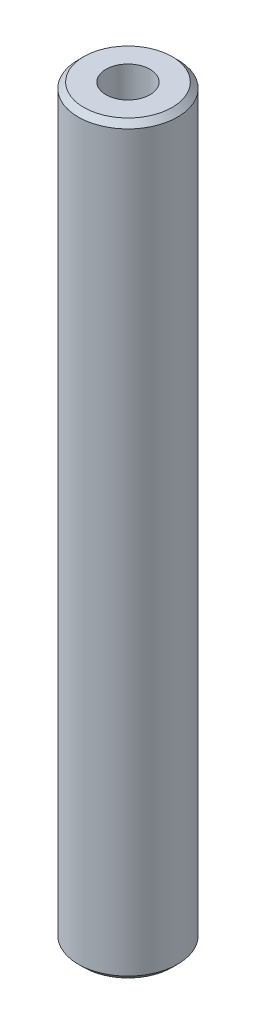
SolidWorks part; units mm, degrees
ref_plane "Front Plane" through (0, 0, 0) normal (0, 0, 1) x (1, 0, 0)
ref_plane "Top Plane" through (0, 0, 0) normal (0, 1, 0) x (1, 0, 0)
ref_plane "Right Plane" through (0, 0, 0) normal (1, 0, 0) x (0, 0, -1)
sketch "Sketch1" plane through (0, 0, 0) normal (0, 1, 0) x (1, 0, 0)
  circle A0 centre (0, 0) radius 40
  dimension "SHAFT_OD" = 80
extrude "Boss-Extrude1" add sketch "Sketch1" along normal blind 600
sketch "Sketch2" plane through (0, 0, 0) normal (0, 1, 0) x (1, 0, 0)
  circle A0 centre (0, 0) radius 17.7651
  dimension "BORE_D" = 35.5302
extrude "Cut-Extrude1" cut sketch "Sketch2" along normal through all
chamfer "Chamfer1" distance 4.4698 angle 45 2 edges at (0, 600, 40) (0, 0, 40)
